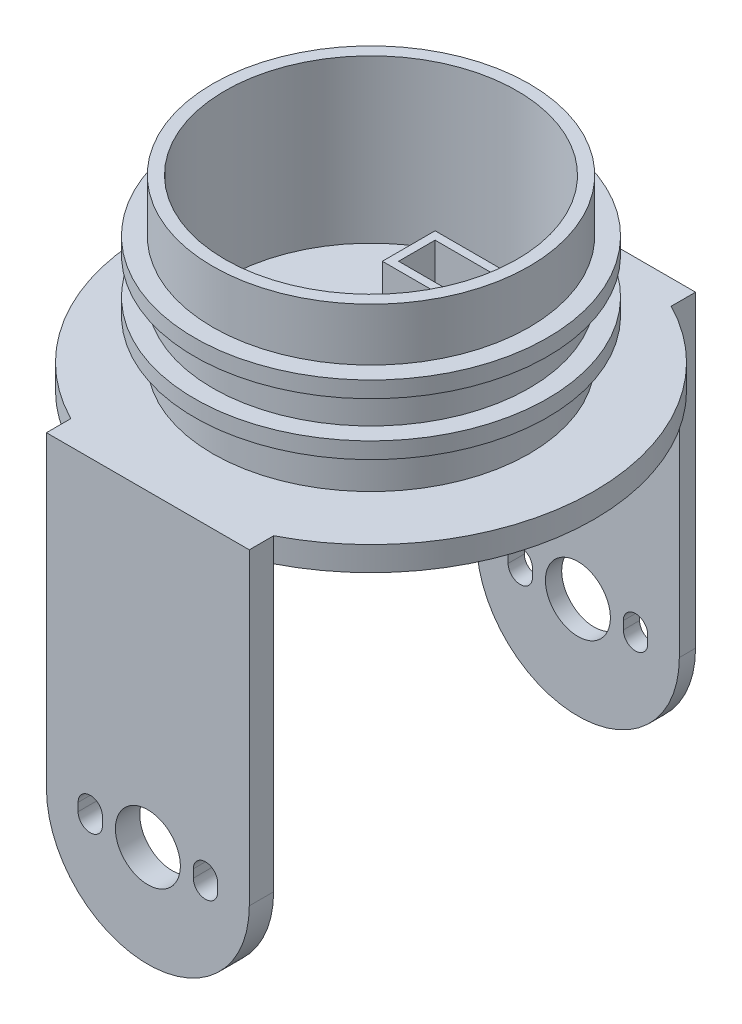
SolidWorks part; units mm, degrees
ref_plane "前基準面" through (0, 0, 0) normal (0, 0, 1) x (1, 0, 0)
ref_plane "上基準面" through (0, 0, 0) normal (0, 1, 0) x (1, 0, 0)
ref_plane "右基準面" through (0, 0, 0) normal (1, 0, 0) x (0, 0, -1)
sketch "草圖1" plane through (0, 0, 0) normal (0, 1, 0) x (1, 0, 0)
  circle A0 centre (0, 0) radius 19.5
  circle A1 centre (0, 0) radius 18
  dimension "D1" = 39
  dimension "D2" = 36
extrude "填料-伸長1" add sketch "草圖1" along normal blind 20
sketch "草圖3" plane through (0, 0, 0) normal (0, -1, 0) x (1, 0, 0)
  circle A0 centre (0, 0) radius 27.5
  dimension "D1" = 55
extrude "填料-伸長2" add sketch "草圖3" along normal blind 3
ref_plane "平面2" through (0, -3, 0) normal (0, -1, 0) x (-1, 0, 0)
ref_plane "平面5" through (0, 0, 0) normal (0, 1, 0) x (1, 0, 0)
ref_plane "平面6" through (0, 7, 0) normal (0, -1, 0) x (-1, 0, 0)
sketch "草圖25" plane through (0, 7, 0) normal (0, -1, 0) x (-1, 0, 0)
  circle A0 centre (0, 0) radius 21.75
  circle A1 centre (0, 0) radius 19.5
  dimension "D1" = 43.5
extrude "填料-伸長12" add sketch "草圖25" along normal blind 2
ref_plane "平面10" through (0, 10.5, 0) normal (0, -1, 0) x (-1, 0, 0)
sketch "草圖26" plane through (0, 10.5, 0) normal (0, -1, 0) x (-1, 0, 0)
  circle A0 centre (0, 0) radius 21.75
  circle A1 centre (0, 0) radius 19.5
extrude "填料-伸長13" add sketch "草圖26" against normal blind 2 from offset 1 offset against normal yes
sketch "草圖27" plane through (0, -3, 0) normal (0, -1, 0) x (1, 0, 0)
  line L0 (0, 0) -> (-12.5, 0)
  line L1 (46.0389, 0) -> (-46.0389, 0) construction
  line L2 (-12.5, 0) -> (-12.5, 25.5)
  line L3 (-12.5, 25.5) -> (12.5, 25.5)
  line L4 (12.5, 25.5) -> (12.5, 0)
  line L5 (12.5, 0) -> (-12.5, 0)
  line L6 (-12.5, 0) -> (-12.5, -25.5)
  line L7 (-12.5, -25.5) -> (12.5, -25.5)
  line L8 (12.5, -25.5) -> (12.5, 0)
  circle M6 centre (0, 0) radius 27.5
extrude "填料-伸長14" add sketch "草圖27" against normal blind 3 contours L8 L5 L0 L6 L7 M6 | L5 L4 L3 L2 L0 M6 | L6 L7 M6 | L7 L8 M6 | L4 L3 M6 | L3 L2 M6 region at (0, -3, -12.7084) region at (0, -3, 12.7084) region at (-11.7799, -3, 25.1714) region at (-11.7799, -3, -25.1714) region at (11.7799, -3, 25.1714) region at (11.7799, -3, -25.1714)
sketch "草圖28" plane through (0, 0, -25.5) normal (0, 0, -1) x (-1, 0, 0)
  line L0 (12.5, -3) -> (12.5, -38)
  line L1 (12.5, -38) -> (-12.5, -38)
  line L2 (-12.5, -38) -> (-12.5, 0)
  line L3 (-12.5, 0) -> (12.5, 0)
  line L4 (12.5, 0) -> (12.5, -3) construction
  line L5 (12.5, 0) -> (12.5, -3)
  line L6 (-7.1, -37.5) -> (-7.1, -38.5) construction
  line L7 (-5.6, -37.5) -> (-5.6, -38.5)
  line L8 (-8.6, -37.5) -> (-8.6, -38.5)
  line L9 (12.5, -3) -> (-12.5, -3)
  line L10 (7.1, -37.5) -> (7.1, -38.5) construction
  line L11 (8.6, -37.5) -> (8.6, -38.5)
  line L12 (5.6, -37.5) -> (5.6, -38.5)
  arc A0 (12.5, -38) -> (-12.5, -38) centre (0, -38) cw
  circle A1 centre (0, -38) radius 4
  arc A2 (-5.6, -37.5) -> (-8.6, -37.5) centre (-7.1, -37.5) ccw
  arc A3 (-8.6, -38.5) -> (-5.6, -38.5) centre (-7.1, -38.5) ccw
  arc A4 (8.6, -37.5) -> (5.6, -37.5) centre (7.1, -37.5) ccw
  arc A5 (5.6, -38.5) -> (8.6, -38.5) centre (7.1, -38.5) ccw
  point P14 (-7.1, -38)
  point P19 (-7.1, -36)
  point P20 (-7.1, -40)
  point P26 (7.1, -38)
  point P31 (7.1, -36)
  point P32 (7.1, -40)
  line M17 (10.2956, 0) -> (10.2956, -3)
  line M18 (10.2956, -3) -> (12.5, -3)
  line M19 (12.5, -3) -> (12.5, 0)
  line M20 (12.5, 0) -> (10.2956, 0)
  dimension "D1" = 8
  dimension "D2" = 4
  dimension "D3" = 3
  dimension "D4" = 5.6
  dimension "D5" = 4
  dimension "D6" = 3
  dimension "D7" = 5.6
  dimension "D8" = 35
extrude "填料-伸長17" add sketch "草圖28" along normal blind 2 contours A4 L11 L1 L0 L9 L2 L8 A2 L7 A1 L12 M18 | L9 L3 L2 M17 | M20 M17 M18 M19 | A5 L12 L1 A1 L7 A3 L8 A0 L11 region at (-11.3978, -1.5, -25.5) region at (0, -19.8277, -25.5) region at (0, -43.9487, -25.5) region at (1.1022, -1.5, -25.5)
extrude "填料-伸長19" add sketch "草圖28<15>" against normal blind 53 contours A4 L11 L1 L0 L9 L2 L8 A2 L7 A1 L12 M18 | A5 L12 L1 A1 L7 A3 L8 A0 L11 region at (0, -19.8277, -25.5) region at (0, -43.9487, -25.5)
sketch "草圖28<15>" plane through (0, 0, -25.5) normal (0, 0, -1) x (-1, 0, 0) same geometry as "草圖28"
sketch "草圖32" plane through (0, 0, 25.5) normal (0, 0, 1) x (1, 0, 0)
  line L0 (10.2956, -3) -> (12.5, -3)
  line L1 (-30.25, -3) -> (30.25, -3) construction
  line L2 (12.5, -3) -> (0, -3) construction
  line L3 (12.5, -3) -> (12.5, 0)
  line L4 (19.5, 0) -> (-19.5, 0) construction
  line L5 (12.5, 0) -> (12.5, -3) construction
  line L6 (12.5, 0) -> (10.2956, 0)
  line L7 (10.2956, 0) -> (10.2956, -3) construction
  line L8 (10.2956, 0) -> (10.2956, -3)
  line L9 (-10.2956, 0) -> (-10.2956, -3)
  line L10 (-10.2956, -3) -> (-10.2956, 0) construction
  line L11 (0, -3) -> (-12.5, -3) construction
  line L12 (-12.5, -3) -> (-10.2956, -3) construction
  line L13 (-10.2956, -3) -> (-12.5, -3)
  line L14 (-12.5, -3) -> (-12.5, 0)
  line L15 (-12.5, -3) -> (-12.5, 0) construction
  line L16 (-12.5, 0) -> (-10.2956, 0)
extrude "填料-伸長20" add sketch "草圖32" along normal blind 2
extrude "除料-伸長8" cut sketch "草圖28<18>" against normal blind 50 contours A4 L11 L1 L0 L9 L2 L8 A2 L7 A1 L12 M18 | A5 L12 L1 A1 L7 A3 L8 A0 L11 region at (0, -19.8277, -25.5) region at (0, -43.9487, -25.5)
sketch "草圖28<18>" plane through (0, 0, -25.5) normal (0, 0, -1) x (-1, 0, 0) same geometry as "草圖28"
sketch "草圖33" plane through (0, 0, 27.5) normal (0, 0, 1) x (1, 0, 0)
  line L0 (-12.5, -3) -> (12.5, -3)
  line L1 (-30.25, -3) -> (30.25, -3) construction
  line L2 (-12.5, -3) -> (-12.5, 0) construction
  line L3 (12.5, 0) -> (12.5, -3) construction
  line L4 (12.5, -3) -> (12.5, 0)
  line L5 (19.5, 0) -> (-19.5, 0) construction
  line L6 (12.5, 0) -> (-12.5, 0)
  line L7 (-12.5, 0) -> (-12.5, -3)
extrude "填料-伸長21" add sketch "草圖33" against normal blind 3
sketch "草圖34" plane through (0, 0, 0) normal (0, 1, 0) x (1, 0, 0)
  line L0 (0, 0) -> (-17.3838, 0) construction
  line L1 (-17.3838, 0) -> (19.1481, 0) construction
  line L2 (0, 0) -> (0, -21.2728) construction
  line L3 (0, -21.2728) -> (0, 19.1859) construction
  line L4 (5.1, 13) -> (-5.1, 13) construction
  line L5 (-4.1, 12) -> (4.1, 12)
  line L6 (-4.1, 12) -> (-4.1, 7.5)
  line L7 (-4.1, 7.5) -> (4.1, 7.5)
  line L8 (4.1, 12) -> (4.1, 7.5)
  line L10 (5.1, 6.5) -> (-5.1, 6.5)
  line L11 (5.1, 6.5) -> (5.1, 13)
  line L12 (5.1, 13) -> (-5.1, 13)
  line L13 (-5.1, 6.5) -> (-5.1, 13)
  point P13 (0, 13)
  dimension "D1" = 8.2
  dimension "D2" = 4.5
  dimension "D3" = 1
  dimension "D4" = 12
  dimension "D5" = 1
  dimension "D6" = 1
  dimension "D7" = 1
extrude "填料-伸長22" add sketch "草圖34" along normal blind 5
sketch "草圖37" plane through (0, 0, 0) normal (0, 1, 0) x (1, 0, 0)
  line L2 (-4.1, 12) -> (4.1, 12)
  line L3 (-4.1, 12) -> (-4.1, 7.5)
  line L4 (-4.1, 7.5) -> (4.1, 7.5)
  line L5 (4.1, 12) -> (4.1, 7.5)
extrude "除料-伸長9" cut sketch "草圖37" against normal blind 5
sketch "草圖38" plane through (0, 0, -27.5) normal (0, 0, -1) x (-1, 0, 0)
  line L0 (-27.5, -3) -> (27.5, -3) construction
  line L1 (0, -9.8) -> (-1, -14.4947) construction
  line L2 (-1, -14.4947) -> (-1.3125, -15.9618) construction
  line L3 (0, 0) -> (0, -50.5) construction
  line L4 (0, -9.8) -> (1, -14.4947) construction
  line L5 (1, -14.4947) -> (1.3125, -15.9618) construction
  line L6 (-1, -14.4947) -> (-1.3125, -15.9618)
  line L7 (1, -14.4947) -> (1.3125, -15.9618)
  arc A0 (-12.5, -38) -> (12.5, -38) centre (0, -38) ccw construction
  circle A2 centre (0, -9.8) radius 4.8
  circle A3 centre (0, -9.8) radius 6.3
  arc A4 (1, -14.4947) -> (-1, -14.4947) centre (0, -9.8) ccw
  dimension "D1" = 6.8
  dimension "D2" = 9.6
  dimension "D3" = 12.6
  dimension "D4" = 2
  dimension "D5" = 1
extrude "填料-伸長23" add sketch "草圖38" against normal blind 9 contours L7 A3 L6 A2 | L6 A3 L7 A2 region at (0, -15.3429, -27.5) region at (1.3296, -15.1913, -27.5)
extrude "除料-伸長10" cut sketch "草圖38<3>" against normal blind 9.5 contours A2 region at (0, -9.8, -27.5)
sketch "草圖38<3>" plane through (0, 0, -27.5) normal (0, 0, -1) x (-1, 0, 0) same geometry as "草圖38"
extrude "填料-伸長24" add sketch "草圖38<4>" along normal blind 3 contours L7 A3 L6 A2 region at (1.3296, -15.1913, -27.5)
sketch "草圖38<4>" plane through (0, 0, -27.5) normal (0, 0, -1) x (-1, 0, 0) same geometry as "草圖38"
